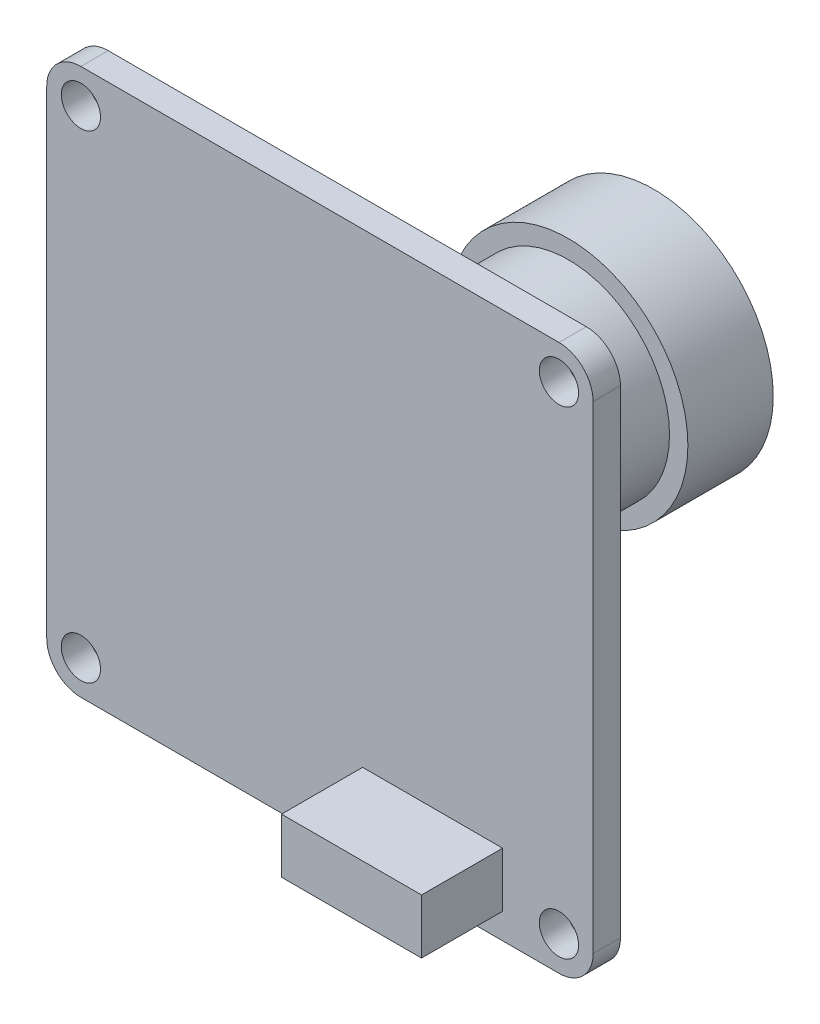
SolidWorks part; units mm, degrees
ref_plane "Front Plane" through (0, 0, 0) normal (0, 0, 1) x (1, 0, 0)
ref_plane "Top Plane" through (0, 0, 0) normal (0, 1, 0) x (1, 0, 0)
ref_plane "Right Plane" through (0, 0, 0) normal (1, 0, 0) x (0, 0, -1)
sketch "Sketch1" plane through (0, 0, 0) normal (0, 0, 1) x (1, 0, 0)
  line L0 (-16, 0) -> (16, 0) construction
  line L1 (16, -16) -> (-16, -16)
  line L2 (16, -16) -> (16, 16)
  line L3 (16, 16) -> (-16, 16)
  line L4 (-16, -16) -> (-16, 16)
  line L5 (16, -16) -> (-16, 16) construction
  line L6 (16, 16) -> (-16, -16) construction
  line L7 (0, 16) -> (0, -16) construction
  line L8 (9, 0) -> (-9, 0) construction
  line L9 (6.5, -6.5) -> (-6.5, -6.5)
  line L10 (6.5, -6.5) -> (6.5, 6.5)
  line L11 (6.5, 6.5) -> (-6.5, 6.5)
  line L12 (-6.5, -6.5) -> (-6.5, 6.5)
  line L13 (6.5, -6.5) -> (-6.5, 6.5) construction
  line L14 (6.5, 6.5) -> (-6.5, -6.5) construction
  line L15 (9, -2) -> (-9, -2)
  line L16 (9, 2) -> (-9, 2)
  circle A0 centre (-14, 14) radius 1.15
  circle A1 centre (14, 14) radius 1.15
  circle A2 centre (14, -14) radius 1.15
  circle A3 centre (-14, -14) radius 1.15
  arc A4 (9, -2) -> (9, 2) centre (9, 0) ccw
  arc A5 (-9, 2) -> (-9, -2) centre (-9, 0) ccw
  circle A6 centre (0, 0) radius 6.5
  point P0 (0, 0)
  point P12 (0, 0)
  point P25 (0, 0)
  dimension "D3" = 2.3
  dimension "D9" = 2
  dimension "D1" = 32
  dimension "D2" = 32
  dimension "D4" = 28
  dimension "D6" = 13
  dimension "D7" = 13
  dimension "D8" = 18
  dimension "D5" = 4
extrude "Boss-Extrude1" add sketch "Sketch1" along normal blind 1.6 contours L4 L1 L2 L3 A5 L16 L12 L11 L10 A4 L15 L9 A3 A2 A1 A0 | A6 L11 L12 L16 | L16 A6 | A6 L16 L10 L11 | L15 A4 L16 L10 | A6 L10 L16 | A6 L15 L10 | A6 L9 L10 L15 | L15 A6 | A6 L15 L12 L9 | L16 A5 L15 L12 | A6 L16 L12 | A6 L12 L15 | L16 A6 L15 region at (0, -15.5475, 0) region at (5.0162, -5.1314, 0) region at (-5.0162, -5.1314, 0) region at (0, -3.8671, 0) region at (6.4058, -1.5025, 0) region at (8.5599, 0, 0) region at (0, 0, 0) region at (-6.4058, -1.5025, 0) region at (6.4058, 1.5025, 0) region at (-8.5599, 0, 0) region at (-6.4058, 1.5025, 0) region at (5.0162, 5.1314, 0) region at (0, 3.8671, 0) region at (-5.0162, 5.1314, 0)
fillet "Fillet1" radius 2 4 edges at (16, 16, 0.8) (16, -16, 0.8) (-16, -16, 0.8) (-16, 16, 0.8)
extrude "Boss-Extrude2" add sketch "Sketch1<3>" against normal blind 4 contours L16 A6 | A6 L16 L10 L11 | A6 L11 L12 L16 | L16 A5 L15 L12 | L16 A6 L15 | A6 L15 L12 L9 | L15 A6 | A6 L9 L10 L15 | A6 L10 L16 | L15 A4 L16 L10 | A6 L15 L10 | A6 L12 L15 | A6 L16 L12 region at (5.0162, -5.1314, 0) region at (-5.0162, -5.1314, 0) region at (0, -3.8671, 0) region at (6.4058, -1.5025, 0) region at (8.5599, 0, 0) region at (0, 0, 0) region at (-6.4058, -1.5025, 0) region at (6.4058, 1.5025, 0) region at (-8.5599, 0, 0) region at (-6.4058, 1.5025, 0) region at (5.0162, 5.1314, 0) region at (0, 3.8671, 0) region at (-5.0162, 5.1314, 0)
sketch "Sketch1<3>" plane through (0, 0, 0) normal (0, 0, 1) x (1, 0, 0) same geometry as "Sketch1"
extrude "Boss-Extrude3" add sketch "Sketch1<4>" against normal blind 7.75 contours L16 A6 | L16 A6 L15 | L15 A6 region at (0, -3.8671, 0) region at (0, 0, 0) region at (0, 3.8671, 0)
sketch "Sketch1<4>" plane through (0, 0, 0) normal (0, 0, 1) x (1, 0, 0) same geometry as "Sketch1"
sketch "Sketch2" plane through (0, 0, 0) normal (1, 0, 0) x (0, 0, -1)
  line L0 (0, 0) -> (17.95, 0) construction
  line L1 (17.95, 0) -> (17.95, 7)
  line L2 (17.95, 7) -> (12.95, 7)
  line L3 (12.95, 7) -> (12.95, 5.925)
  line L4 (12.95, 5.925) -> (7.75, 5.925)
  line L5 (7.75, -6.5) -> (7.75, 6.5) construction
  line L6 (7.75, 5.925) -> (7.75, 0)
  line L7 (17.95, 0) -> (7.75, 0)
  dimension "D1" = 11.85
  dimension "D2" = 14
  dimension "D3" = 5.2
  dimension "D4" = 5
revolve "Revolve1" add sketch "Sketch2" angle 360 about L0
sketch "Sketch3" plane through (0, 0, 1.6) normal (0, 0, 1) x (1, 0, 0)
  line L0 (16, -14) -> (16, 14) construction
  line L1 (10.7, -14.5) -> (2.5, -14.5)
  line L2 (10.7, -14.5) -> (10.7, -11.3)
  line L3 (10.7, -11.3) -> (2.5, -11.3)
  line L4 (2.5, -14.5) -> (2.5, -11.3)
  dimension "D1" = 8.2
  dimension "D2" = 3.2
  dimension "D3" = 14.5
  dimension "D4" = 13.5
extrude "Boss-Extrude4" add sketch "Sketch3" along normal blind 4.75
